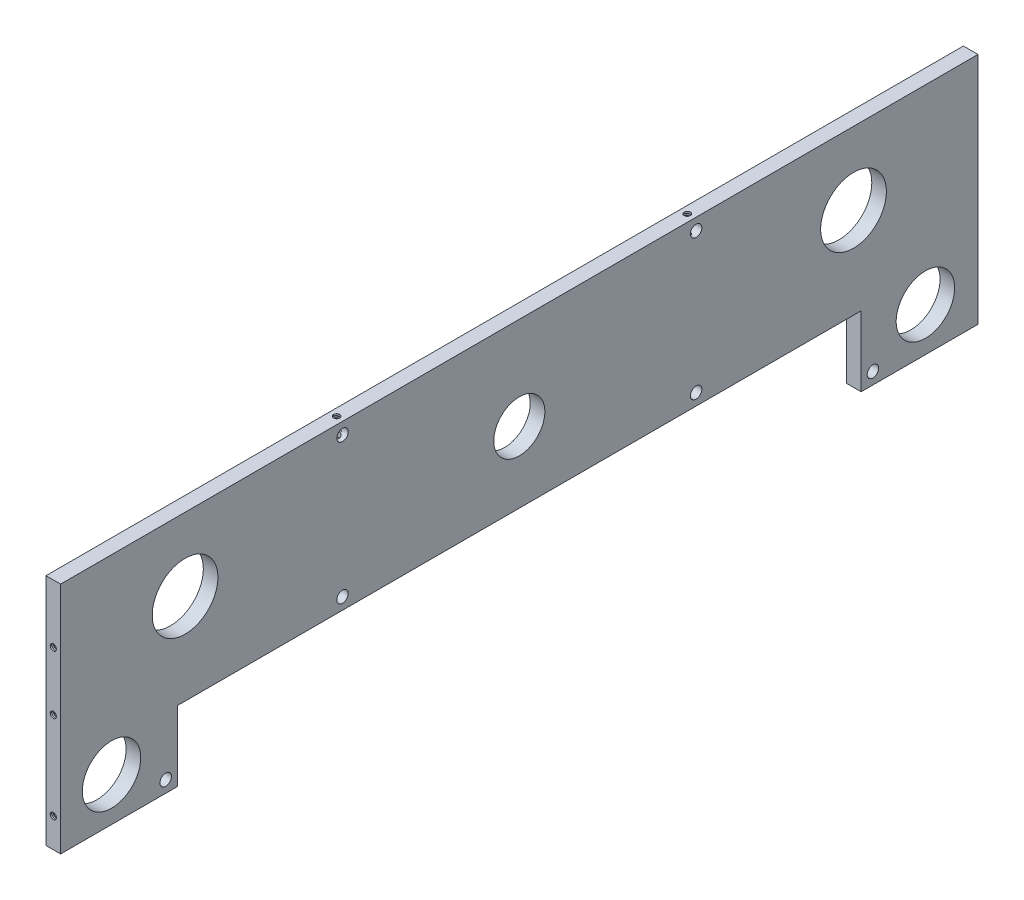
SolidWorks part; units mm, degrees
material "6061-T6 (SS)"
ref_plane "Front Plane" through (0, 0, 0) normal (0, 0, 1) x (1, 0, 0)
ref_plane "Top Plane" through (0, 0, 0) normal (0, 1, 0) x (1, 0, 0)
ref_plane "Right Plane" through (0, 0, 0) normal (1, 0, 0) x (0, 0, -1)
sketch "Sketch1" plane through (0, 0, 0) normal (1, 0, 0) x (0, 0, -1)
  line L1 (-199.39, 50.8) -> (199.39, 50.8)
  line L2 (-199.39, 50.8) -> (-199.39, -50.8)
  line L3 (-199.39, -50.8) -> (199.39, -50.8)
  line L4 (199.39, 50.8) -> (199.39, -50.8)
  line L5 (-199.39, 50.8) -> (199.39, -50.8) construction
  line L6 (-199.39, -50.8) -> (199.39, 50.8) construction
  point P0 (0, 0)
  dimension "D1" = 101.6
  dimension "D2" = 398.78
extrude "Boss-Extrude1" add sketch "Sketch1" along normal blind 6.35
sketch "Sketch2" plane through (6.35, 0, 0) normal (1, 0, 0) x (0, 0, -1)
  line L0 (-199.39, -50.8) -> (199.39, -50.8) construction
  line L1 (-145.2858, 19.1748) -> (0, 10.4973) construction
  line L2 (199.39, 50.8) -> (-199.39, 50.8) construction
  line L3 (0, 10.4973) -> (145.2858, 19.1748) construction
  line L4 (2.4449, 27.4682) -> (-141.1117, 48.1494) construction
  line L5 (0.4075, -6.6439) -> (-144.5902, -10.0906) construction
  line L10 (1.5901, 21.5351) -> (-141.9664, 42.2162) construction
  line L11 (-199.39, 50.8) -> (-199.39, -50.8) construction
  line L12 (-148.59, -50.8) -> (0, -50.8)
  line L13 (-148.59, -50.8) -> (-148.59, -20.32)
  line L14 (-148.59, -20.32) -> (148.59, -20.32)
  line L15 (0, -50.8) -> (0, -20.32) construction
  line L16 (199.39, -50.8) -> (199.39, 50.8) construction
  line L17 (-162.4251, -40.5407) -> (-132.2012, 11.5885) construction
  line L18 (0.265, -0.6512) -> (-144.7326, -4.0979) construction
  line L19 (-177.2583, -31.9405) -> (-199.39, -31.9405) construction
  line L20 (-177.2583, -31.9405) -> (-158.1418, -43.0925) construction
  line L21 (148.59, -50.8) -> (148.59, -20.32)
  line L22 (0, -50.8) -> (148.59, -50.8)
  line L23 (-77.0202, -8.4844) -> (-76.9825, -10.0714) construction
  line L24 (-77.5914, 40.6024) -> (-77.8178, 39.0311) construction
  circle A1 centre (-145.2858, 19.1748) radius 14.2875
  circle A2 centre (145.2858, 19.1748) radius 14.2875
  circle A3 centre (-145.2858, 19.1748) radius 29.2737 construction
  circle A4 centre (0, 10.4973) radius 30.48 construction
  circle A5 centre (145.2858, 19.1748) radius 29.2737 construction
  circle A11 centre (-177.2583, -31.9405) radius 12.7
  circle A12 centre (176.53, -31.9405) radius 12.7
  circle A13 centre (0, 10.4973) radius 11.1125
  circle A14 centre (-177.2583, -31.9405) radius 20.6375 construction
  circle A15 centre (-177.2583, -31.9405) radius 17.1461 construction
  circle A16 centre (-145.2858, 19.1748) radius 15.1248 construction
  circle A17 centre (0, 10.4973) radius 17.1461 construction
  circle A18 centre (34.3662, 10.4973) radius 8.7754 construction
  circle A19 centre (-153.715, -45.675) radius 5.125 construction
  circle A20 centre (-153.715, -45.675) radius 2.4892
  circle A21 centre (-76.8607, 45.675) radius 5.125 construction
  circle A22 centre (-76.8607, -15.195) radius 5.125 construction
  circle A23 centre (-76.8607, -15.195) radius 2.4892
  circle A24 centre (-76.8607, 45.675) radius 2.4892
  circle A25 centre (76.8607, 45.675) radius 2.4892
  circle A26 centre (76.8607, -15.195) radius 2.4892
  circle A27 centre (153.715, -45.675) radius 2.4892
  circle A28 centre (34.3662, 10.4973) radius 22.15 construction
  point P11 (0, 0)
  point P12 (0, -19.9827)
  point P14 (0, 40.9773)
  point P52 (-197.8958, -31.9405)
  point P56 (-159.5733, 19.1748)
  point P74 (0, 0)
  dimension "D1" = 28.575
  dimension "D5" = 58.5474
  dimension "D7" = 9.8227
  dimension "D14" = 25.4
  dimension "D15" = 60.2911
  dimension "D17" = 25.4
  dimension "D20" = 22.225
  dimension "D21" = 28.575
  dimension "D22" = 60.96
  dimension "D23" = 41.275
  dimension "D27" = 34.2921
  dimension "D28" = 30.2496
  dimension "D12" = 17.5508
  dimension "D13" = 10.25
  dimension "D29" = 4.9784
  dimension "D26" = 1.5875
  dimension "D30" = 4.9784
  dimension "D31" = 44.3
  dimension "D3" = 39.8167
  dimension "D4" = 145.5447
  dimension "D6" = 0
  dimension "D8" = 0.3373
  dimension "D9" = 5.9944
  dimension "D10" = 5.9944
  dimension "D11" = 34.3662
  dimension "D16" = 1.4942
  dimension "D18" = 18.8595
  dimension "D19" = 22.86
  dimension "D24" = 30.48
  dimension "D25" = 50.8
extrude "Cut-Extrude1" cut sketch "Sketch2" against normal through all
sketch "Sketch3" plane through (6.35, 0, 0) normal (1, 0, 0) x (0, 0, -1)
  line L0 (-193.294, 19.05) -> (-193.294, -19.05) construction
  line L1 (-199.39, 50.8) -> (-199.39, -50.8) construction
  point P2 (-193.294, 0)
  point P3 (-199.39, 0)
  dimension "D1" = 38.1
  dimension "D2" = 6.096
sketch "Sketch24" plane through (0, 50.8, 0) normal (0, 1, 0) x (1, 0, 0)
  line L0 (6.35, 199.39) -> (0, 199.39) construction
  line L1 (6.35, -199.39) -> (0, -199.39) construction
  line L2 (6.35, 199.39) -> (6.35, -199.39) construction
  point P0 (3.175, 76.2)
  point P1 (3.175, -76.2)
  dimension "D1" = 123.19
  dimension "D2" = 123.19
  dimension "D3" = 3.175
hole_wizard "#36 (0.1065) Diameter Hole1" positions "Sketch25" profile "Sketch26" hole size "#36" standard "ANSI Inch"
sketch "Sketch25" plane through (0, 50.8, 0) normal (0, 1, 0) x (1, 0, 0)
  point P0 (3.175, 76.2)
  point P3 (3.175, -76.2)
sketch "Sketch26" plane through (3.175, 50.8, -76.2) normal (1, 0, 0) x (0, 0, 1)
  line L0 (0, 0) -> (0, 9.7027)
  line L1 (0, 9.7027) -> (1.3525, 8.89)
  line L2 (1.3525, 8.89) -> (1.3525, 0)
  line L5 (1.3525, 0) -> (0, 0)
  line L10 (0, 9.7027) -> (-1.3526, 8.89) construction
  line L11 (0, -6.35) -> (0, 107.95) construction
  dimension "Hole Dia." = 2.7051
  dimension "Hole Depth" = 8.89
  dimension "Drill Angle" = 118
thread "Thread1" pitch 0.7937 method cut profile "Thread Profile1" start angle 0, offset 0, length 6.35, pitch 0.7937, diameter 2.7051
ref_plane "Plane1" through (1.8225, 50.8, -76.2) normal (0, 0, 1) x (-1, 0, 0)
sketch "Thread Profile1" plane through (1.8225, 50.8, -76.2) normal (0, 0, 1) x (-1, 0, 0)
  line L0 (0, 0) -> (0, 0.7937) construction
  line L1 (0, 0) -> (0.4296, 0.248)
  line L2 (0.4296, 0.248) -> (0.4296, 0.3473)
  line L3 (0.4296, 0.3473) -> (0, 0.5953)
  line L4 (0.4296, 0.2977) -> (0, 0.2977) construction
  line L11 (0, 0) -> (0, 0.5953)
  point P2 (0, 0)
  dimension "Pitch" = 0.7937
  dimension "Profile_Angle" = 60
  dimension "Profile_Land" = 0.0992
  dimension "Profile_Height" = 0.4296
thread "Thread2" pitch 0.7937 method cut profile "Thread Profile2" start angle 0, offset 0, length 6.35, pitch 0.7937, diameter 2.7051
ref_plane "Plane2" through (1.8225, 50.8, 76.2) normal (0, 0, 1) x (-1, 0, 0)
sketch "Thread Profile2" plane through (1.8225, 50.8, 76.2) normal (0, 0, 1) x (-1, 0, 0)
  line L0 (0, 0) -> (0, 0.7937) construction
  line L1 (0, 0) -> (0.4296, 0.248)
  line L2 (0.4296, 0.248) -> (0.4296, 0.3473)
  line L3 (0.4296, 0.3473) -> (0, 0.5953)
  line L4 (0.4296, 0.2977) -> (0, 0.2977) construction
  line L11 (0, 0) -> (0, 0.5953)
  point P2 (0, 0)
  dimension "Pitch" = 0.7937
  dimension "Profile_Angle" = 60
  dimension "Profile_Land" = 0.0992
  dimension "Profile_Height" = 0.4296
sketch "Sketch27" plane through (0, 0, -199.39) normal (0, 0, -1) x (-1, 0, 0)
  line L0 (-6.35, 50.8) -> (0, 50.8) construction
  line L1 (-6.35, -50.8) -> (-6.35, 50.8) construction
  point P0 (-3.175, 25.4)
  point P1 (-3.175, 0)
  point P2 (-3.175, -38.1)
  dimension "D1" = 25.4
  dimension "D2" = 3.175
hole_wizard "#36 (0.1065) Diameter Hole2" positions "Sketch28" profile "Sketch29" hole size "#36" standard "ANSI Inch"
sketch "Sketch28" plane through (0, 0, -199.39) normal (0, 0, -1) x (-1, 0, 0)
  point P0 (-3.175, 25.4)
  point P3 (-3.175, 0)
  point P6 (-3.175, -38.1)
sketch "Sketch29" plane through (3.175, 25.4, -199.39) normal (1, 0, 0) x (0, 1, 0)
  line L0 (0, 0) -> (0, 9.7027)
  line L1 (0, 9.7027) -> (1.3525, 8.89)
  line L2 (1.3525, 8.89) -> (1.3525, 0)
  line L5 (1.3525, 0) -> (0, 0)
  line L10 (0, 9.7027) -> (-1.3526, 8.89) construction
  line L11 (0, -6.35) -> (0, 107.95) construction
  dimension "Hole Dia." = 2.7051
  dimension "Hole Depth" = 8.89
  dimension "Drill Angle" = 118
thread "Thread3" pitch 0.7937 method cut profile "Thread Profile3" start angle 0, offset 0, length 6.35, pitch 0.7937, diameter 2.7051
ref_plane "Plane3" through (4.5275, 25.4, -199.39) normal (0, -1, 0) x (1, 0, 0)
sketch "Thread Profile3" plane through (4.5275, 25.4, -199.39) normal (0, -1, 0) x (1, 0, 0)
  line L0 (0, 0) -> (0, 0.7937) construction
  line L1 (0, 0) -> (0.4296, 0.248)
  line L2 (0.4296, 0.248) -> (0.4296, 0.3473)
  line L3 (0.4296, 0.3473) -> (0, 0.5953)
  line L4 (0.4296, 0.2977) -> (0, 0.2977) construction
  line L11 (0, 0) -> (0, 0.5953)
  point P2 (0, 0)
  dimension "Pitch" = 0.7937
  dimension "Profile_Angle" = 60
  dimension "Profile_Land" = 0.0992
  dimension "Profile_Height" = 0.4296
thread "Thread4" pitch 0.7937 method cut profile "Thread Profile4" start angle 0, offset 0, length 6.35, pitch 0.7937, diameter 2.7051
ref_plane "Plane4" through (4.5275, 0, -199.39) normal (0, -1, 0) x (1, 0, 0)
sketch "Thread Profile4" plane through (4.5275, 0, -199.39) normal (0, -1, 0) x (1, 0, 0)
  line L0 (0, 0) -> (0, 0.7937) construction
  line L1 (0, 0) -> (0.4296, 0.248)
  line L2 (0.4296, 0.248) -> (0.4296, 0.3473)
  line L3 (0.4296, 0.3473) -> (0, 0.5953)
  line L4 (0.4296, 0.2977) -> (0, 0.2977) construction
  line L11 (0, 0) -> (0, 0.5953)
  point P2 (0, 0)
  dimension "Pitch" = 0.7937
  dimension "Profile_Angle" = 60
  dimension "Profile_Land" = 0.0992
  dimension "Profile_Height" = 0.4296
thread "Thread5" pitch 0.7937 method cut profile "Thread Profile5" start angle 0, offset 0, length 6.35, pitch 0.7937, diameter 2.7051
ref_plane "Plane5" through (4.5275, -38.1, -199.39) normal (0, -1, 0) x (1, 0, 0)
sketch "Thread Profile5" plane through (4.5275, -38.1, -199.39) normal (0, -1, 0) x (1, 0, 0)
  line L0 (0, 0) -> (0, 0.7937) construction
  line L1 (0, 0) -> (0.4296, 0.248)
  line L2 (0.4296, 0.248) -> (0.4296, 0.3473)
  line L3 (0.4296, 0.3473) -> (0, 0.5953)
  line L4 (0.4296, 0.2977) -> (0, 0.2977) construction
  line L11 (0, 0) -> (0, 0.5953)
  point P2 (0, 0)
  dimension "Pitch" = 0.7937
  dimension "Profile_Angle" = 60
  dimension "Profile_Land" = 0.0992
  dimension "Profile_Height" = 0.4296
sketch "Sketch36" plane through (0, 0, 199.39) normal (0, 0, 1) x (1, 0, 0)
  line L0 (6.35, 50.8) -> (6.35, -50.8) construction
  point P0 (3.175, 25.4)
  point P1 (3.175, -12.7)
  point P2 (3.175, -50.8)
  dimension "D1" = 25.4
  dimension "D2" = 3.175
  dimension "D3" = 38.1
  dimension "D4" = 38.1
hole_wizard "#36 (0.1065) Diameter Hole3" positions "Sketch37" profile "Sketch38" hole size "#36" standard "ANSI Inch"
sketch "Sketch37" plane through (0, 0, 199.39) normal (0, 0, 1) x (1, 0, 0)
  point P0 (3.175, 25.4)
  point P3 (3.175, 0)
  point P6 (3.175, -38.1)
sketch "Sketch38" plane through (3.175, 25.4, 199.39) normal (1, 0, 0) x (0, -1, 0)
  line L0 (0, 0) -> (0, 9.7027)
  line L1 (0, 9.7027) -> (1.3525, 8.89)
  line L2 (1.3525, 8.89) -> (1.3525, 0)
  line L5 (1.3525, 0) -> (0, 0)
  line L10 (0, 9.7027) -> (-1.3525, 8.89) construction
  line L11 (0, -6.35) -> (0, 107.95) construction
  dimension "Hole Dia." = 2.7051
  dimension "Hole Depth" = 8.89
  dimension "Drill Angle" = 118
thread "Thread6" pitch 0.7937 method cut profile "Thread Profile6" start angle 0, offset 0, length 6.35, pitch 0.7937, diameter 2.7051
ref_plane "Plane6" through (1.8225, 25.4, 199.39) normal (0, -1, 0) x (-1, 0, 0)
sketch "Thread Profile6" plane through (1.8225, 25.4, 199.39) normal (0, -1, 0) x (-1, 0, 0)
  line L0 (0, 0) -> (0, 0.7937) construction
  line L1 (0, 0) -> (0.4296, 0.248)
  line L2 (0.4296, 0.248) -> (0.4296, 0.3473)
  line L3 (0.4296, 0.3473) -> (0, 0.5953)
  line L4 (0.4296, 0.2977) -> (0, 0.2977) construction
  line L11 (0, 0) -> (0, 0.5953)
  point P2 (0, 0)
  dimension "Pitch" = 0.7937
  dimension "Profile_Angle" = 60
  dimension "Profile_Land" = 0.0992
  dimension "Profile_Height" = 0.4296
thread "Thread7" pitch 0.7937 method cut profile "Thread Profile7" start angle 0, offset 0, length 6.35, pitch 0.7937, diameter 2.7051
ref_plane "Plane7" through (1.8225, 0, 199.39) normal (0, -1, 0) x (-1, 0, 0)
sketch "Thread Profile7" plane through (1.8225, 0, 199.39) normal (0, -1, 0) x (-1, 0, 0)
  line L0 (0, 0) -> (0, 0.7937) construction
  line L1 (0, 0) -> (0.4296, 0.248)
  line L2 (0.4296, 0.248) -> (0.4296, 0.3473)
  line L3 (0.4296, 0.3473) -> (0, 0.5953)
  line L4 (0.4296, 0.2977) -> (0, 0.2977) construction
  line L11 (0, 0) -> (0, 0.5953)
  point P2 (0, 0)
  dimension "Pitch" = 0.7937
  dimension "Profile_Angle" = 60
  dimension "Profile_Land" = 0.0992
  dimension "Profile_Height" = 0.4296
thread "Thread8" pitch 0.7937 method cut profile "Thread Profile8" start angle 0, offset 0, length 6.35, pitch 0.7937, diameter 2.7051
ref_plane "Plane8" through (1.8225, -38.1, 199.39) normal (0, -1, 0) x (-1, 0, 0)
sketch "Thread Profile8" plane through (1.8225, -38.1, 199.39) normal (0, -1, 0) x (-1, 0, 0)
  line L0 (0, 0) -> (0, 0.7937) construction
  line L1 (0, 0) -> (0.4296, 0.248)
  line L2 (0.4296, 0.248) -> (0.4296, 0.3473)
  line L3 (0.4296, 0.3473) -> (0, 0.5953)
  line L4 (0.4296, 0.2977) -> (0, 0.2977) construction
  line L11 (0, 0) -> (0, 0.5953)
  point P2 (0, 0)
  dimension "Pitch" = 0.7937
  dimension "Profile_Angle" = 60
  dimension "Profile_Land" = 0.0992
  dimension "Profile_Height" = 0.4296
